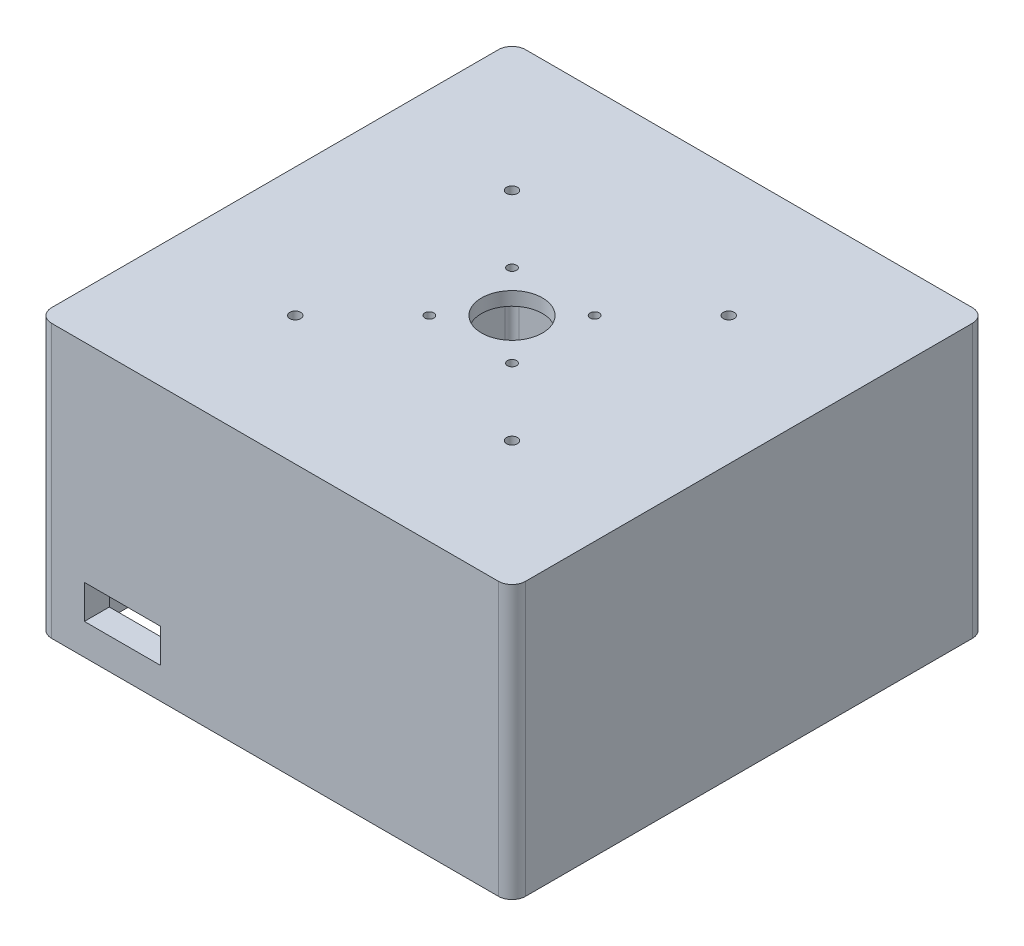
SolidWorks part; units mm, degrees
ref_plane "Front Plane" through (0, 0, 0) normal (0, 0, 1) x (1, 0, 0)
ref_plane "Top Plane" through (0, 0, 0) normal (0, 1, 0) x (1, 0, 0)
ref_plane "Right Plane" through (0, 0, 0) normal (1, 0, 0) x (0, 0, -1)
sketch "Sketch1" plane through (0, 0, 0) normal (0, 1, 0) x (1, 0, 0)
  line L1 (-88.9, -88.9) -> (88.9, -88.9)
  line L2 (-88.9, -88.9) -> (-88.9, 88.9)
  line L3 (-88.9, 88.9) -> (88.9, 88.9)
  line L4 (88.9, -88.9) -> (88.9, 88.9)
  line L5 (-88.9, -88.9) -> (88.9, 88.9) construction
  line L6 (-88.9, 88.9) -> (88.9, -88.9) construction
  line L11 (-64.7359, -64.7359) -> (-18.5761, -18.5761) construction
  line L12 (-23.0799, 23.0799) -> (23.0799, -23.0799) construction
  line L13 (-79.5394, -79.5394) -> (79.5394, -79.5394)
  line L14 (-79.5394, -79.5394) -> (-79.5394, 79.5394)
  line L15 (-79.5394, 79.5394) -> (79.5394, 79.5394)
  line L16 (79.5394, -79.5394) -> (79.5394, 79.5394)
  line L17 (-79.5394, -79.5394) -> (79.5394, 79.5394) construction
  line L18 (-79.5394, 79.5394) -> (79.5394, -79.5394) construction
  circle A0 centre (0, 0) radius 11.43
  point P0 (0, 0)
  point P6 (0, 0)
  point P11 (0, 0)
  dimension "D3" = 22.86
  dimension "D1" = 177.8
extrude "Boss-Extrude1" add sketch "Sketch1" along normal blind 38.1 and the other way blind 59.182 contours L1 L4 L3 L2 L16 L13 L14 L15 region at (-86.3855, 0, 0)
extrude "Boss-Extrude3" add sketch "Sketch1<5>" along normal blind 5.08 from surface contours L1 L4 L3 L2 L16 L13 L14 L15 | L13 L16 L15 L14 region at (-86.3855, 0, 0) region at (-77.2897, 0, 0) starting at face at (0, 38.1, 0)
sketch "Sketch1<5>" plane through (0, 0, 0) normal (0, 1, 0) x (1, 0, 0) same geometry as "Sketch1"
fillet "Fillet1" radius 5.08 4 edges at (88.9, -8.001, -88.9) (-88.9, -8.001, -88.9) (88.9, -8.001, 88.9) (-88.9, -8.001, 88.9)
sketch "Sketch3" plane through (0, 43.18, 0) normal (0, 1, 0) x (1, 0, 0)
  line L0 (0, 88.9) -> (0, -88.9) construction
  line L2 (-88.9, 0) -> (88.9, 0) construction
  line L3 (88.9, 83.82) -> (88.9, -83.82) construction
  line L4 (83.82, -88.9) -> (-83.82, -88.9) construction
  circle A0 centre (-15.5, 15.5) radius 1.7
  circle A1 centre (-15.5, -15.5) radius 1.7
  circle A2 centre (15.5, 15.5) radius 1.7
  circle A3 centre (15.5, -15.5) radius 1.7
  point P7 (0, 0)
  point P14 (0, 0)
  point P15 (0, 0)
  dimension "D1" = 3.4
  dimension "D2" = 15.5
  dimension "D3" = 15.5
extrude "Cut-Extrude1" cut sketch "Sketch3" against normal through all
fillet "Fillet2" radius 2.54 4 edges at (-79.5394, -10.541, -79.5394) (-79.5394, -10.541, 79.5394) (79.5394, -10.541, 79.5394) (79.5394, -10.541, -79.5394)
sketch "Sketch4" plane through (0, 43.18, 0) normal (0, 1, 0) x (1, 0, 0)
  line L0 (0, 88.9) -> (0, -88.9) construction
  line L1 (83.82, -88.9) -> (-83.82, -88.9) construction
  line L2 (-88.9, 0) -> (88.9, 0) construction
  line L3 (88.9, 83.82) -> (88.9, -83.82) construction
  circle A0 centre (-40.66, 40.66) radius 2.05
  circle A1 centre (40.66, 40.66) radius 2.05
  circle A2 centre (-40.66, -40.66) radius 2.05
  circle A3 centre (40.66, -40.66) radius 2.05
  point P7 (0, 0)
  point P14 (0, 0)
  dimension "D1" = 4.1
  dimension "D2" = 40.66
  dimension "D3" = 40.66
extrude "Cut-Extrude2" cut sketch "Sketch4" against normal up to surface (5.08 mm away) up to face at (15.5, 38.1, 13.8)
sketch "Sketch5" plane through (0, 0, 88.9) normal (0, 0, 1) x (1, 0, 0)
  line L1 (-71.5107, -34.8243) -> (-42.9357, -34.8243)
  line L2 (-71.5107, -34.8243) -> (-71.5107, -47.5243)
  line L3 (-71.5107, -47.5243) -> (-42.9357, -47.5243)
  line L4 (-42.9357, -34.8243) -> (-42.9357, -47.5243)
  dimension "D1" = 28.575
  dimension "D2" = 12.7
extrude "Cut-Extrude3" cut sketch "Sketch5" against normal up to surface (9.3606 mm away) up to face at (0, -10.541, 79.5394)
